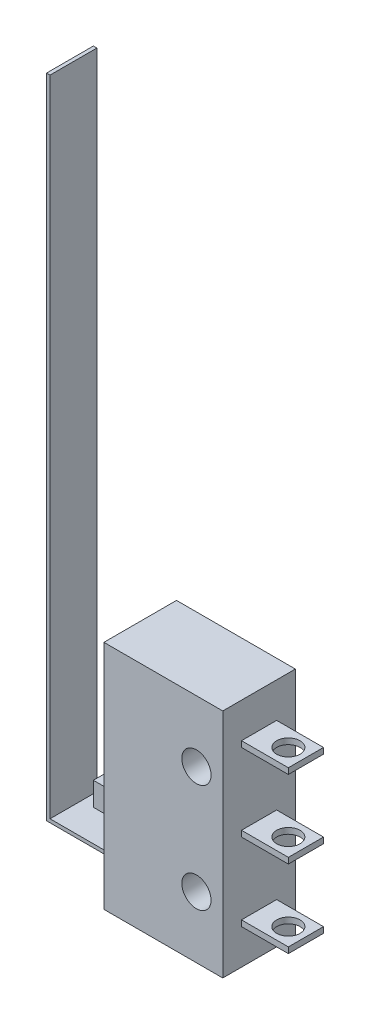
SolidWorks part; units mm, degrees
ref_plane "Front Plane" through (0, 0, 0) normal (0, 0, 1) x (1, 0, 0)
ref_plane "Top Plane" through (0, 0, 0) normal (0, 1, 0) x (1, 0, 0)
ref_plane "Right Plane" through (0, 0, 0) normal (1, 0, 0) x (0, 0, -1)
sketch "Sketch1" plane through (0, 0, 0) normal (0, 0, 1) x (1, 0, 0)
  line L1 (0, 0) -> (10.15, 0)
  line L2 (0, 0) -> (0, 19.75)
  line L3 (0, 19.75) -> (10.15, 19.75)
  line L4 (10.15, 0) -> (10.15, 19.75)
  dimension "D1" = 10.15
  dimension "D2" = 19.75
extrude "Boss-Extrude1" add sketch "Sketch1" against normal blind 6.2
sketch "Sketch2" plane through (0, 0, 0) normal (-1, 0, 0) x (0, 0, 1)
  line L0 (-6.2, 6) -> (0, 6) construction
  line L1 (-6.2, 19.75) -> (-6.2, 0) construction
  line L2 (0, 19.75) -> (0, 0) construction
  line L3 (-6.2, 0) -> (0, 0) construction
  line L4 (-3.1, 8) -> (-3.1, 6) construction
  line L5 (-5.1, 6) -> (-1.1, 6)
  line L6 (-5.1, 6) -> (-5.1, 8)
  line L7 (-5.1, 8) -> (-1.1, 8)
  line L8 (-1.1, 6) -> (-1.1, 8)
  line L9 (-3.1, 0) -> (-3.1, 2.9878) construction
  dimension "D1" = 6
  dimension "D2" = 4
  dimension "D4" = 2
extrude "Boss-Extrude2" add sketch "Sketch2" along normal blind 2
sketch "Sketch3" plane through (0, 0, 0) normal (-1, 0, 0) x (0, 0, 1)
  line L0 (-6.2, 3) -> (0, 3) construction
  line L1 (-6.2, 19.75) -> (-6.2, 0) construction
  line L2 (0, 19.75) -> (0, 0) construction
  line L3 (-6.2, 0) -> (0, 0) construction
  line L4 (-3.1, 0) -> (-3.1, 1.9674) construction
  line L5 (-5.1, 3) -> (-1.1, 3)
  line L6 (-5.1, 3) -> (-5.1, 3.3)
  line L7 (-5.1, 3.3) -> (-1.1, 3.3)
  line L8 (-1.1, 3) -> (-1.1, 3.3)
  line L9 (-3.1, 3.3) -> (-3.1, 3) construction
  dimension "D1" = 3
  dimension "D2" = 4
  dimension "D4" = 0.3
extrude "Boss-Extrude3" add sketch "Sketch3" along normal blind 6
sketch "Sketch4" plane through (0, 3.3, 0) normal (0, 1, 0) x (1, 0, 0)
  line L0 (-6, 1.1) -> (0, 1.1) construction
  line L1 (-6, 5.1) -> (-5.7, 5.1)
  line L2 (-6, 5.1) -> (-6, 1.1)
  line L3 (-6, 1.1) -> (-5.7, 1.1)
  line L4 (-5.7, 5.1) -> (-5.7, 1.1)
  dimension "D1" = 0.3
extrude "Boss-Extrude4" add sketch "Sketch4" along normal blind 55
sketch "Sketch5" plane through (10.15, 0, 0) normal (1, 0, 0) x (0, 0, -1)
  line L0 (3.1, 19.75) -> (3.1, 0) construction
  line L1 (6.2, 19.75) -> (0, 19.75) construction
  line L2 (6.2, 0) -> (0, 0) construction
  line L4 (1.6, 3.5) -> (4.6, 3.5)
  line L5 (1.6, 3.5) -> (1.6, 3)
  line L6 (1.6, 3) -> (4.6, 3)
  line L7 (4.6, 3.5) -> (4.6, 3)
  line L8 (1.6, 3.5) -> (4.6, 3) construction
  line L9 (1.6, 3) -> (4.6, 3.5) construction
  line L10 (1.6, 10.125) -> (4.6, 10.125)
  line L11 (1.6, 10.125) -> (1.6, 9.625)
  line L12 (1.6, 9.625) -> (4.6, 9.625)
  line L13 (4.6, 10.125) -> (4.6, 9.625)
  line L14 (1.6, 10.125) -> (4.6, 9.625) construction
  line L15 (1.6, 9.625) -> (4.6, 10.125) construction
  line L16 (1.6, 16.75) -> (4.6, 16.75)
  line L17 (1.6, 16.75) -> (1.6, 16.25)
  line L18 (1.6, 16.25) -> (4.6, 16.25)
  line L19 (4.6, 16.75) -> (4.6, 16.25)
  line L20 (1.6, 16.75) -> (4.6, 16.25) construction
  line L21 (1.6, 16.25) -> (4.6, 16.75) construction
  point P6 (3.1, 3.25)
  point P11 (3.1, 9.875)
  point P16 (3.1, 16.5)
  point P21 (3.1, 9.875)
  dimension "D1" = 0.5
  dimension "D2" = 0.5
  dimension "D3" = 0.5
  dimension "D4" = 3
  dimension "D5" = 3
  dimension "D6" = 3
  dimension "D7" = 3
  dimension "D8" = 3
extrude "Boss-Extrude5" add sketch "Sketch5" along normal blind 4
sketch "Sketch6" plane through (0, 16.75, 0) normal (0, 1, 0) x (1, 0, 0)
  line L0 (14.15, 3.1) -> (10.15, 3.1) construction
  line L1 (14.15, 4.6) -> (14.15, 1.6) construction
  line L2 (10.15, 4.6) -> (10.15, 1.6) construction
  circle A0 centre (12.65, 3.1) radius 1
  dimension "D1" = 2
  dimension "D2" = 1.5
extrude "Cut-Extrude1" cut sketch "Sketch6" against normal through all
sketch "Sketch7" plane through (0, 0, 0) normal (0, 0, 1) x (1, 0, 0)
  line L0 (10.15, 0) -> (10.15, 19.75) construction
  line L1 (0, 0) -> (10.15, 0) construction
  line L2 (10.15, 19.75) -> (0, 19.75) construction
  circle A0 centre (7.9, 5.25) radius 1.25
  circle A1 centre (7.9, 14.5) radius 1.25
  dimension "D1" = 2.5
  dimension "D2" = 2.5
  dimension "D3" = 2.25
  dimension "D4" = 2.25
  dimension "D5" = 5.25
  dimension "D6" = 5.25
extrude "Cut-Extrude2" cut sketch "Sketch7" against normal through all
sketch "Sketch8" plane through (0, 0, 0) normal (0, 0, 1) x (1, 0, 0)
  line L0 (7.9, 15.75) -> (7.9, 13.25) construction
  line L1 (6.65, 14.5) -> (9.15, 14.5) construction
  line L2 (7.9, 6.5) -> (7.9, 4) construction
  line L3 (6.65, 5.25) -> (9.15, 5.25) construction
  circle A0 centre (7.9, 14.5) radius 1.25 construction
  circle A1 centre (7.9, 5.25) radius 1.25 construction
sketch "Sketch9" plane through (0, 0, -6.2) normal (0, 0, -1) x (-1, 0, 0)
  line L0 (-7.9, 15.75) -> (-7.9, 13.25) construction
  line L1 (-6.65, 14.5) -> (-9.15, 14.5) construction
  line L2 (-7.9, 6.5) -> (-7.9, 4) construction
  line L3 (-9.15, 5.25) -> (-6.65, 5.25) construction
